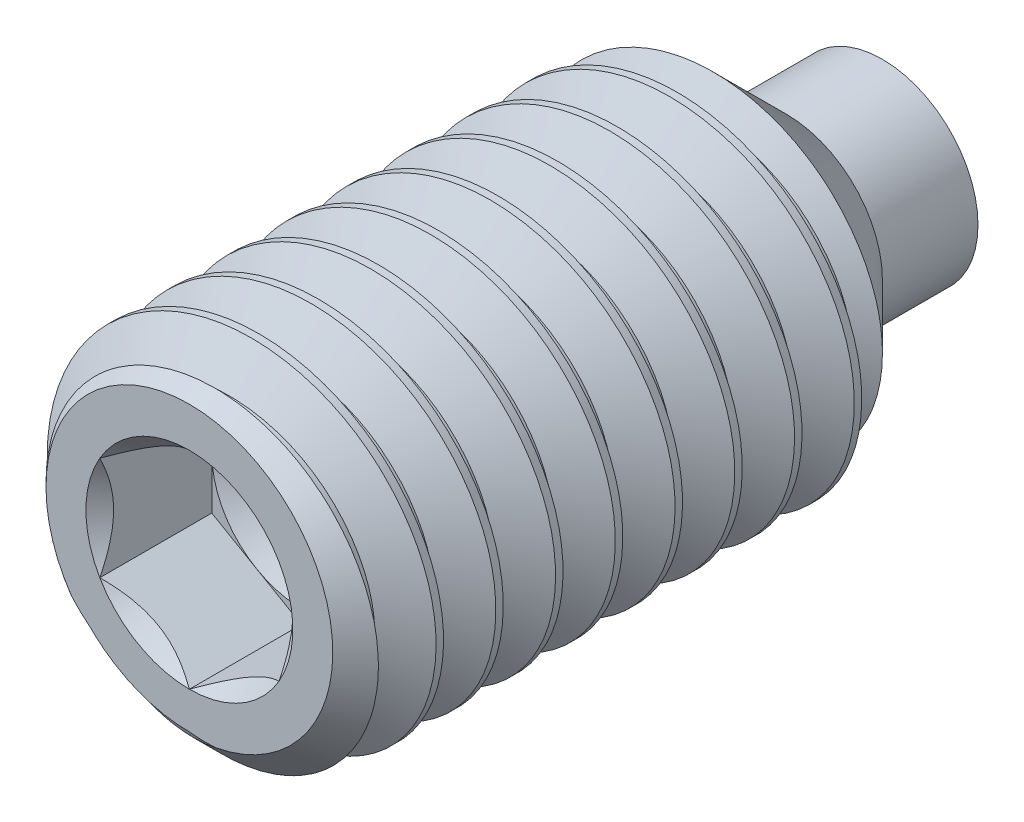
SolidWorks part; units mm, degrees
ref_plane "Front" through (0, 0, 0) normal (0, 0, 1) x (1, 0, 0)
ref_plane "Top" through (0, 0, 0) normal (0, 1, 0) x (1, 0, 0)
ref_plane "Right" through (0, 0, 0) normal (1, 0, 0) x (0, 0, -1)
sketch "Sketch22" plane through (0, 0, 0) normal (1, 0, 0) x (0, 0, -1)
  line L0 (-11.6, 0) -> (-11.6, 2.4)
  line L1 (-11.6, 2.4) -> (-11, 3)
  line L2 (-11, 3) -> (-3, 3)
  line L3 (-3, 3) -> (-1.6, 1.6)
  line L5 (0, 0) -> (-11.6, 0)
  line L9 (-12.7, 0) -> (10.3, 0) construction
  line L10 (-1.6, 1.6) -> (0, 1.6)
  line L11 (0, 1.6) -> (0, 0)
  dimension "D3" = 45
  dimension "B" = 1.6
  dimension "Length" = 10
  dimension "D1" = 3.2
  dimension "D2" = 6
  dimension "D4" = 4.8
  dimension "D5" = 45
revolve "Revolve1" add sketch "Sketch22" angle 360 about L9
ref_plane "Plane2" through (0, 0, 1.6) normal (0, 0, 1) x (1, 0, 0)
sketch "Sketch27" plane through (0, 0, 1.6) normal (0, 0, 1) x (1, 0, 0)
  circle A0 centre (0, 0) radius 3
curve "Helix/Spiral1" pitch 1 height 11 radius 3 centre (0, 0, 1.6) axis (0, 0, 1) start towards (0, 1, 0)
sketch "Sketch6" plane through (0, 0, 0) normal (1, 0, 0) x (0, 0, -1)
  line L0 (-1.4125, 2.6752) -> (-0.9125, 2.6752) construction
  line L3 (-11, 3) -> (-3, 3) construction
  line L4 (-1.1, 2.3505) -> (-1.225, 2.3505)
  line L5 (-1.225, 2.3505) -> (-1.6, 3)
  line L6 (-1.1, 2.3505) -> (-0.725, 3)
  line L7 (-0.725, 3) -> (-1.6, 3)
  dimension "D2" = 0.125
  dimension "D3" = 60
  dimension "D1" = 0.5
sweep "Cut-Sweep1" cut profiles "Sketch6" path "Helix/Spiral1" align with end faces yes
sketch "Sketch30" plane through (0, 0, 11.6) normal (0, 0, 1) x (1, 0, 0)
  line L1 (1.5, -0.866) -> (1.5, 0.866)
  line L2 (1.5, 0.866) -> (0, 1.7321)
  line L3 (0, 1.7321) -> (-1.5, 0.866)
  line L4 (-1.5, 0.866) -> (-1.5, -0.866)
  line L5 (-1.5, -0.866) -> (0, -1.7321)
  line L6 (0, -1.7321) -> (1.5, -0.866)
  circle A0 centre (0, 0) radius 1.5 construction
  dimension "hex" = 3
extrude "Cut-Extrude1" cut sketch "Sketch30" against normal blind 1.875
sketch "Sketch31" plane through (0, 0, 11.6) normal (0, 0, 1) x (1, 0, 0)
  circle A0 centre (0, 0) radius 1.7321
extrude "Cut-Extrude2" cut sketch "Sketch31" against normal through all draft 45
sketch "Sketch32" plane through (0, 0, 9.725) normal (0, 0, 1) x (1, 0, 0)
  circle A0 centre (0, 0) radius 1.5 construction
  circle A1 centre (0, 0) radius 1.5
extrude "Cut-Extrude3" cut sketch "Sketch32" against normal through all draft 60
equation "\"D3@Helix/Spiral1\" = \"Length@Sketch22\" + \"D4@Helix/Spiral1\""
equation "\"D2@Sketch6\" = \"D4@Helix/Spiral1\" * .125"
equation "\"D1@Sketch6\" = \"D4@Helix/Spiral1\" * .5"
equation "\"D1@Cut-Extrude1\" = \"hex@Sketch30\" * .625"
